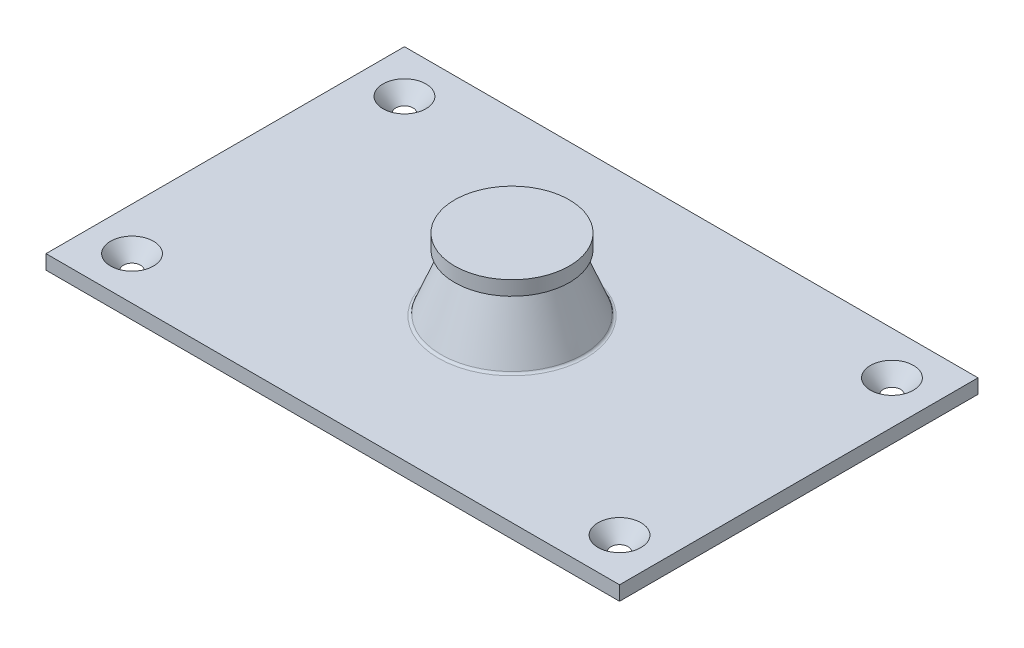
SolidWorks part; units mm, degrees
material "Alloy Steel (SS)"
ref_plane "Front Plane" through (0, 0, 0) normal (0, 0, 1) x (1, 0, 0)
ref_plane "Top Plane" through (0, 0, 0) normal (0, 1, 0) x (1, 0, 0)
ref_plane "Right Plane" through (0, 0, 0) normal (1, 0, 0) x (0, 0, -1)
sketch "Sketch1" plane through (0, 0, 0) normal (0, 1, 0) x (1, 0, 0)
  line L1 (-25.4, -15.875) -> (25.4, -15.875)
  line L2 (-25.4, -15.875) -> (-25.4, 15.875)
  line L3 (-25.4, 15.875) -> (25.4, 15.875)
  line L4 (25.4, -15.875) -> (25.4, 15.875)
  line L5 (-25.4, -15.875) -> (25.4, 15.875) construction
  line L6 (-25.4, 15.875) -> (25.4, -15.875) construction
  point P0 (0, 0)
  dimension "D1" = 50.8
  dimension "D2" = 31.75
extrude "Boss-Extrude1" add sketch "Sketch1" along normal blind 1.27
sketch "Sketch2" plane through (0, 1.27, 0) normal (0, 1, 0) x (1, 0, 0)
  circle A0 centre (0, 0) radius 6.35
  dimension "D1" = 12.7
extrude "Boss-Extrude2" add sketch "Sketch2" along normal blind 6.35 and the other way blind 1.27
chamfer "Chamfer1" distance 6.35 distance2 2.54 1 edges at (0, 7.62, 6.35) first distance on face at (0, 7.62, 6.35)
fillet "Fillet1" radius 0.254 1 edges at (0, 1.27, -6.35)
sketch "Sketch5" plane through (0, 0, 15.875) normal (0, 0, 1) x (1, 0, 0)
  line L0 (21.59, -1.6227) -> (21.59, 4.81) construction
  line L1 (25.4, 1.27) -> (25.4, 0) construction
  line L2 (21.59, 0) -> (20.828, 0)
  line L3 (-25.4, 0) -> (25.4, 0) construction
  line L4 (20.828, 0) -> (19.685, 1.27)
  line L5 (-25.4, 1.27) -> (25.4, 1.27) construction
  line L6 (19.685, 1.27) -> (21.59, 1.27)
  line L7 (21.59, 1.27) -> (21.59, 0)
  dimension "D1" = 3.81
  dimension "D2" = 1.905
  dimension "D3" = 0.762
ref_plane "Plane1" through (0, 0, 12.065) normal (0, 0, 1) x (1, 0, 0)
sketch "Sketch6" plane through (0, 0, 12.065) normal (0, 0, 1) x (1, 0, 0)
  line L0 (21.59, 1.27) -> (21.59, 0) construction
  line L1 (19.685, 1.27) -> (21.59, 1.27) construction
  line L2 (20.828, 0) -> (19.685, 1.27) construction
  line L3 (21.59, 0) -> (20.828, 0) construction
  line L4 (21.59, 1.27) -> (21.59, 0)
  line L5 (19.685, 1.27) -> (21.59, 1.27)
  line L6 (20.828, 0) -> (19.685, 1.27)
  line L7 (21.59, 0) -> (20.828, 0)
revolve "Cut-Revolve1" cut sketch "Sketch6" angle 360 about L4
mirror "Mirror1" about plane through (0, 0, 0) normal (0, 0, 1) of "Cut-Revolve1"
mirror "Mirror2" about plane through (0, 0, 0) normal (1, 0, 0) of "Mirror1"
sketch "Sketch7" plane through (0, 7.62, 0) normal (0, 1, 0) x (1, 0, 0)
  circle A0 centre (0, 0) radius 5.08
  dimension "D1" = 10.16
extrude "Boss-Extrude3" add sketch "Sketch7" against normal blind 1.27
